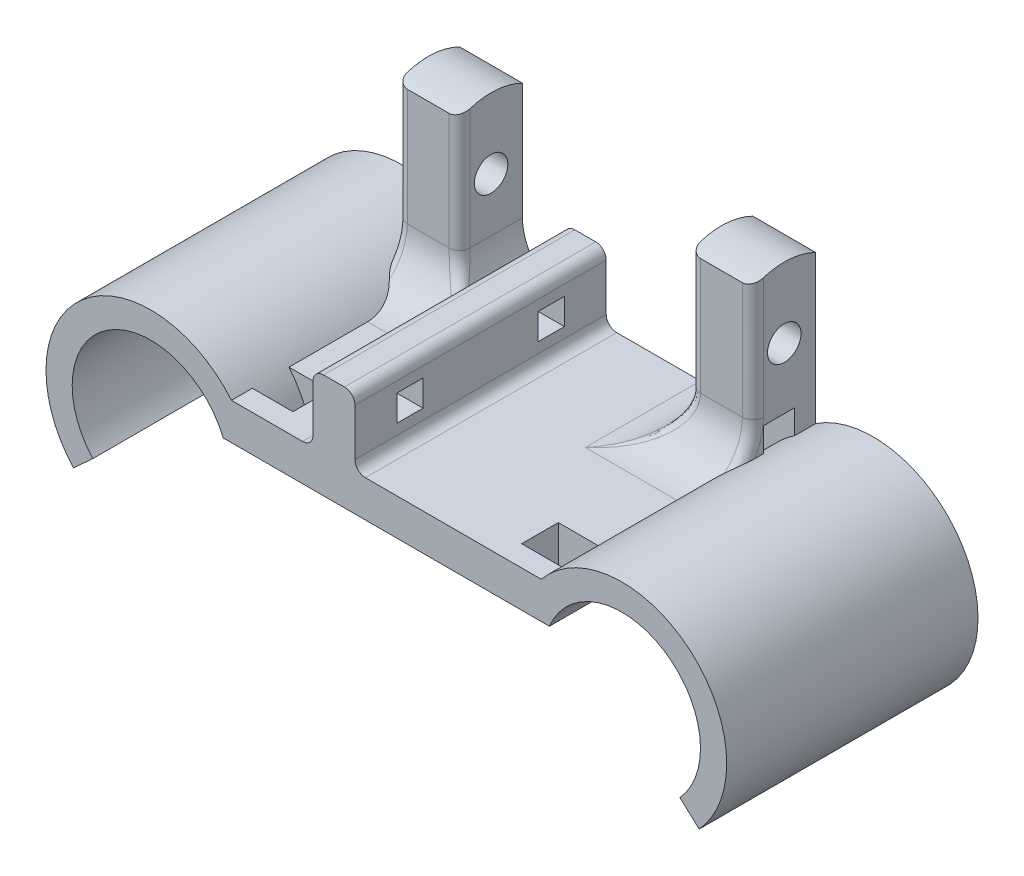
SolidWorks part; units mm, degrees
ref_plane "Front" through (0, 0, 0) normal (0, 0, 1) x (1, 0, 0)
ref_plane "Top" through (0, 0, 0) normal (0, 1, 0) x (1, 0, 0)
ref_plane "Right" through (0, 0, 0) normal (1, 0, 0) x (0, 0, -1)
sketch "Sketch1" plane through (0, 0, 0) normal (0, 0, 1) x (1, 0, 0)
  line L0 (-28.0296, -7.9371) -> (-22.5, -2.8701) construction
  line L1 (-22.5, -2.8701) -> (-15.5709, 0) construction
  line L2 (-22.5, -2.8701) -> (-22.5, 4.6299) construction
  arc A0 (-15.5709, 0) -> (-28.0296, -7.9371) centre (-22.5, -2.8701) ccw
  dimension "D2" = 7.5
  dimension "D1" = 22.5
  dimension "D3" = 200
  dimension "D4" = 67.5
extrude "Extrude-LM8UU Cup" add sketch "Sketch1" along normal blind 24 thin thin type one direction wall 2.5
sketch "Sketch2" plane through (0, 0, 0) normal (0, 0, 1) x (1, 0, 0)
  line L0 (0, 0) -> (-15.5709, 0)
extrude "Extrude-Straight" add sketch "Sketch2" along normal through all thin thin type one direction wall 3.5
sketch "Sketch5" plane through (0, 0, 24) normal (0, 0, 1) x (1, 0, 0)
  line L0 (0, 0) -> (-15.5709, 0) construction
  line L1 (-12.9207, 0) -> (-10.9207, 0)
  line L2 (-10.9207, 0) -> (-10.9207, 3.5)
  line L3 (0, 3.5) -> (-14.7915, 3.5) construction
  line L4 (-10.9207, 3.5) -> (-14.7915, 3.5)
  arc A0 (-14.7915, 3.5) -> (-12.9207, 0) centre (-22.5, -2.8701) cw
  arc A1 (-14.7915, 3.5) -> (-29.8728, -9.626) centre (-22.5, -2.8701) ccw construction
  dimension "D1" = 2
extrude "Cut-Upper Zip Tie" cut sketch "Sketch5" against normal blind 3.5 from offset 2 offset against normal yes
mirror "Mirror-Cup And Straight" about plane through (0, 0, 0) normal (1, 0, 0) of "Extrude-LM8UU Cup", "Extrude-Straight", "Cut-Upper Zip Tie"
sketch "Sketch6" plane through (0, 0, 0) normal (1, 0, 0) x (0, 0, -1)
  line L1 (-6, 3.5) -> (0, 3.5)
  line L2 (-6, 3.5) -> (-6, 15.6299)
  line L3 (-6, 15.6299) -> (0, 15.6299)
  line L4 (0, 3.5) -> (0, 15.6299)
  dimension "D1" = 6
  dimension "D2" = 18.5
extrude "Boss-Rod Attachments" add sketch "Sketch6" along normal blind 6 from offset 11
sketch "Sketch7" plane through (11, 0, 0) normal (-1, 0, 0) x (0, 0, 1)
  line L0 (3, 15.6299) -> (3, 13.6299) construction
  line L1 (0, 15.6299) -> (6, 15.6299) construction
  circle A0 centre (3, 13.6299) radius 1.6
  dimension "D2" = 3.2
  dimension "D1" = 16.5
extrude "Cut-Rod Screw Hole" cut sketch "Sketch7" against normal through all
sketch "Sketch8" plane through (11, 0, 0) normal (-1, 0, 0) x (0, 0, 1)
  line L0 (0, 15.6299) -> (6, 15.6299)
  line L1 (0, 15.6299) -> (0, 19.6299)
  line L2 (0, 19.6299) -> (6, 19.6299) construction
  line L3 (6, 19.6299) -> (6, 15.6299)
  arc A0 (0, 19.6299) -> (6, 19.6299) centre (3, 13.6299) cw
  dimension "D1" = 4
extrude "Boss-Rod Round End" add sketch "Sketch8" against normal up to surface (6 mm away) up to face at (17, 13.6299, 4.6)
mirror "Mirror-Rod Attachment" about plane through (0, 0, 0) normal (1, 0, 0) of "Boss-Rod Round End", "Cut-Rod Screw Hole", "Boss-Rod Attachments"
fillet "Fillet1" radius 5 4 edges at (12.8957, 3.5, 6) (-12.8957, 3.5, 6) (-11, 3.5, 3) (11, 3.5, 3)
fillet "Fillet2" radius 1 8 edges at (9.5355, 4.9645, 7.4645) (-9.5355, 4.9645, 7.4645) (11, 14.0649, 6) (-11, 14.0649, 6) (17, 6.9079, 6.2603) (-17, 14.0649, 6) (17, 14.0649, 6) (-17, 6.9079, 6.2603)
sketch "Sketch9" plane through (0, 0, 0) normal (1, 0, 0) x (0, 0, -1)
  line L1 (0, 0) -> (-24, 0)
  line L2 (0, 0) -> (0, 10)
  line L3 (0, 10) -> (-24, 10)
  line L4 (-24, 0) -> (-24, 10)
  dimension "D1" = 10
extrude "Boss-Spectra Mount" add sketch "Sketch9" against normal blind 4 from offset 3 offset against normal yes
sketch "Sketch10" plane through (-7, 0, 0) normal (-1, 0, 0) x (0, 0, 1)
  line L1 (17.5, 8) -> (20, 8)
  line L2 (17.5, 8) -> (17.5, 5.5)
  line L3 (17.5, 5.5) -> (20, 5.5)
  line L4 (20, 8) -> (20, 5.5)
  line L5 (24, 10) -> (24, 3.5) construction
  line L6 (11, 3.5) -> (24, 3.5) construction
  dimension "D1" = 2.5
  dimension "D2" = 2
  dimension "D3" = 4
extrude "Cut-Spectra Hole" cut sketch "Sketch10" against normal up to surface (4 mm away) up to face at (-3, 6.75, 12)
pattern_linear "LPattern-Spectra Holes" count 1 spacing 4 along (0, 1, 0) count 2 spacing 13.5 along (0, 0, -1) of "Cut-Spectra Hole"
fillet "Fillet3" radius 1 7 edges at (-7, 3.601, 4.9) (-7, 3.5175, 10.5819) (-7, 3.5, 17.5) (-3, 3.5, 12) (-3, 10, 12) (-7, 10, 12)
sketch "Sketch11" plane through (0, 0, 0) normal (0, 0, -1) x (-1, 0, 0)
  line L0 (-17, 5.4815) -> (-17, 19.6299) construction
  line L1 (-15.5709, 0) -> (15.5709, 0) construction
  line L2 (-17, 7.7952) -> (-21.7869, 7.1044)
  line L3 (-12.9207, 0) -> (-10.8483, 0)
  arc A0 (-12.9207, 0) -> (-14.7915, 3.5) centre (-22.5, -2.8701) ccw construction
  arc A1 (-12.9207, 0) -> (-21.7869, 7.1044) centre (-22.5, -2.8701) ccw
  arc A2 (-10.8483, 0) -> (-17, 7.7952) centre (-22.5, -2.8701) ccw
  arc A3 (-11.0049, 0.574) -> (-21.6442, 9.0993) centre (-22.5, -2.8701) ccw construction
  arc A4 (-17, 5.4815) -> (-29.8728, -9.626) centre (-22.5, -2.8701) ccw construction
  dimension "D1" = 2
extrude "Cut-Lower Zip Tie" cut sketch "Sketch11" against normal blind 3 from offset 2 offset against normal yes
mirror "Mirror-Lower Zip Tie" about plane through (0, 0, 0) normal (1, 0, 0) of "Cut-Lower Zip Tie"
sketch "Sketch13" plane through (0, 0, 0) normal (0, 0, -1) x (-1, 0, 0)
  circle A0 centre (0, 13) radius 3.5
  dimension "D1" = 7
  dimension "D2" = 13
extrude "Boss-Magnet Boss" [suppressed] add sketch "Sketch13" against normal blind 3.5
sketch "Sketch12" [suppressed] plane through (0, 0, 0) normal (0, 0, -1) x (-1, 0, 0)
  circle A0 centre (0, 13) radius 2.5
  arc A1 (2.8723, 15) -> (0, 9.5) centre (0, 13) ccw construction
  dimension "D1" = 5
extrude "Cut-Magnet Slot" [suppressed] cut sketch "Sketch12" against normal blind 2.5
